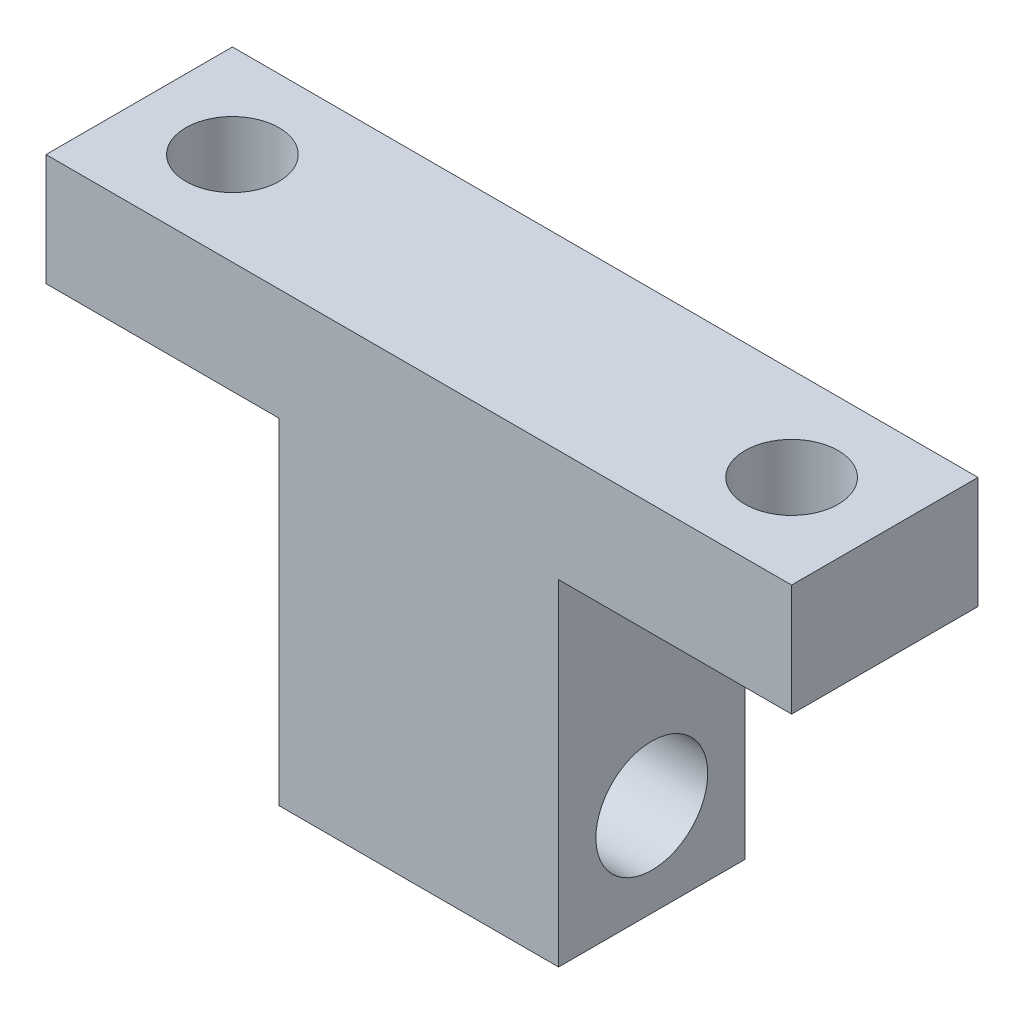
SolidWorks part; units mm, degrees
ref_plane "Front" through (0, 0, 0) normal (0, 0, 1) x (1, 0, 0)
ref_plane "Top" through (0, 0, 0) normal (0, 1, 0) x (1, 0, 0)
ref_plane "Right" through (0, 0, 0) normal (1, 0, 0) x (0, 0, -1)
sketch "草图1" plane through (0, 0, 0) normal (0, 0, 1) x (1, 0, 0)
  line L0 (-20, 0) -> (20, 0)
  line L1 (20, 0) -> (20, -6)
  line L2 (20, -6) -> (7.5, -6)
  line L3 (7.5, -6) -> (7.5, -24)
  line L4 (7.5, -24) -> (-7.5, -24)
  line L5 (-7.5, -24) -> (-7.5, -6)
  line L6 (-7.5, -6) -> (-20, -6)
  line L7 (-20, -6) -> (-20, 0)
  point P4 (0, 0)
  dimension "D1" = 40
  dimension "D2" = 15
  dimension "D3" = 6
  dimension "D4" = 24
extrude "凸台-拉伸1" add sketch "草图1" along normal blind 10
sketch "草图2" plane through (0, -6, 0) normal (0, -1, 0) x (1, 0, 0)
  line L0 (20, 10) -> (20, 0) construction
  circle A0 centre (15, 5) radius 2.5
  point P2 (26.9573, 5.1473)
  point P5 (20, 5)
  dimension "D1" = 5
  dimension "D2" = 5
extrude "切除-拉伸1" cut sketch "草图2" against normal through all
mirror "镜向1" about plane through (0, 0, 0) normal (1, 0, 0) of "切除-拉伸1"
sketch "草图3" plane through (7.5, 0, 0) normal (1, 0, 0) x (0, 0, -1)
  line L0 (-10, -24) -> (0, -24) construction
  circle A0 centre (-5, -19) radius 3
  dimension "D1" = 6
  dimension "D2" = 5
extrude "切除-拉伸2" cut sketch "草图3" against normal through all
